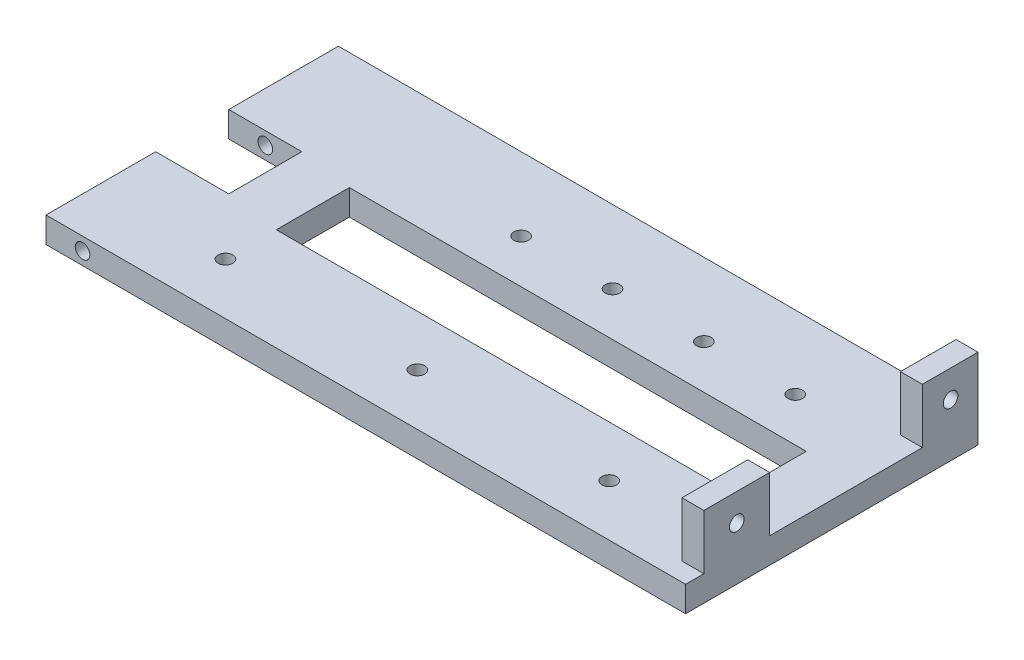
SolidWorks part; units mm, degrees
ref_plane "Front Plane" through (0, 0, 0) normal (0, 0, 1) x (1, 0, 0)
ref_plane "Top Plane" through (0, 0, 0) normal (0, 1, 0) x (1, 0, 0)
ref_plane "Right Plane" through (0, 0, 0) normal (1, 0, 0) x (0, 0, -1)
sketch "Sketch1" plane through (0, 0, 0) normal (0, 1, 0) x (1, 0, 0)
  line L1 (-89.8834, 33.007) -> (85.1166, 33.007)
  line L2 (-89.8834, 33.007) -> (-89.8834, -46.993)
  line L3 (-89.8834, -46.993) -> (85.1166, -46.993)
  line L4 (85.1166, 33.007) -> (85.1166, -46.993)
  dimension "D1" = 80
  dimension "D2" = 175
extrude "Boss-Extrude1" add sketch "Sketch1" along normal blind 7
sketch "Sketch2" plane through (0, 7, 0) normal (0, 1, 0) x (1, 0, 0)
  line L0 (-89.8834, -46.993) -> (85.1166, -46.993) construction
  line L1 (-89.8834, 33.007) -> (-89.8834, -46.993) construction
  line L2 (85.1166, -46.993) -> (85.1166, 33.007) construction
  circle A0 centre (-54.8834, -32.893) radius 2
  circle A1 centre (-2.3834, -32.893) radius 2
  circle A2 centre (50.1166, -32.893) radius 2
  dimension "D1" = 14.1
  dimension "D2" = 14.1
  dimension "D3" = 14.1
  dimension "D4" = 35
  dimension "D5" = 52.5
  dimension "D6" = 52.5
  dimension "D7" = 35
extrude "Cut-Extrude1" cut sketch "Sketch2" against normal blind 10
sketch "Sketch3" plane through (0, 7, 0) normal (0, 1, 0) x (1, 0, 0)
  line L1 (50.1166, -18.993) -> (-74.8834, -18.993)
  line L2 (50.1166, -18.993) -> (50.1166, 1.007)
  line L3 (50.1166, 1.007) -> (-74.8834, 1.007)
  line L4 (-74.8834, -18.993) -> (-74.8834, 1.007)
  line L6 (-89.8834, -46.993) -> (85.1166, -46.993) construction
  line L7 (-89.8834, 33.007) -> (-89.8834, -46.993) construction
  dimension "D1" = 125
  dimension "D2" = 28
  dimension "D3" = 15
  dimension "D4" = 20
extrude "Cut-Extrude2" cut sketch "Sketch3" against normal blind 1
sketch "Sketch7" plane through (0, 7, 0) normal (0, 1, 0) x (1, 0, 0)
  line L0 (-89.8834, 33.007) -> (-89.8834, -46.993) construction
  line L1 (-89.8834, 33.007) -> (-83.8834, 33.007)
  line L2 (-89.8834, 33.007) -> (-89.8834, 17.7803)
  line L3 (-89.8834, 17.7803) -> (-83.8834, 17.7803)
  line L4 (-83.8834, 33.007) -> (-83.8834, 17.7803)
  line L5 (-89.8834, -41.993) -> (-83.8834, -41.993)
  line L6 (-89.8834, -41.993) -> (-89.8834, -23.993)
  line L7 (-89.8834, -23.993) -> (-83.8834, -23.993)
  line L8 (-83.8834, -41.993) -> (-83.8834, -23.993)
  line L9 (-89.8834, -46.993) -> (85.1166, -46.993) construction
  dimension "D1" = 6
  dimension "D2" = 15.2267
  dimension "D3" = 5
  dimension "D4" = 18
  dimension "D5" = 6
extrude "Boss-Extrude3" add sketch "Sketch7" along normal blind 15
sketch "Sketch8" plane through (-83.8834, 0, 0) normal (1, 0, 0) x (0, 0, -1)
  line L0 (33.007, 22) -> (33.007, 7) construction
  line L1 (17.7803, 22) -> (33.007, 22) construction
  line L2 (-23.993, 22) -> (-23.993, 7) construction
  circle A0 centre (25.507, 14.5) radius 2
  circle A1 centre (-32.993, 14.5) radius 2
  dimension "D1" = 7.5
  dimension "D3" = 9
  dimension "D2" = 7.5
extrude "Cut-Extrude4" cut sketch "Sketch8" against normal blind 15
sketch "Sketch9" plane through (0, 0, 0) normal (0, -1, 0) x (1, 0, 0)
  line L0 (85.1166, 46.993) -> (85.1166, -33.007) construction
  line L1 (85.1166, 16.993) -> (65.1166, 16.993)
  line L2 (85.1166, 16.993) -> (85.1166, -3.007)
  line L3 (85.1166, -3.007) -> (65.1166, -3.007)
  line L4 (65.1166, 16.993) -> (65.1166, -3.007)
  line L5 (-89.8834, 46.993) -> (85.1166, 46.993) construction
  line L6 (85.1166, -33.007) -> (-89.8834, -33.007) construction
  dimension "D1" = 20
  dimension "D2" = 20
  dimension "D3" = 30
  dimension "D4" = 30
extrude "Cut-Extrude5" cut sketch "Sketch9" against normal blind 15
sketch "Sketch10" plane through (0, 0, -3.007) normal (0, 0, 1) x (1, 0, 0)
  line L0 (85.1166, 7) -> (85.1166, 0) construction
  line L1 (65.1166, 0) -> (85.1166, 0) construction
  circle A0 centre (75.1166, 3.5) radius 2
  dimension "D1" = 10
  dimension "D2" = 3.5
extrude "Cut-Extrude7" cut sketch "Sketch10" against normal through all both and the other way through all
extrude "Cut-Extrude8" cut sketch "Sketch3<3>" against normal blind 10
sketch "Sketch3<3>" plane through (0, 7, 0) normal (0, 1, 0) x (1, 0, 0) same geometry as "Sketch3"
sketch "Sketch11" plane through (0, 7, 0) normal (0, 1, 0) x (1, 0, 0)
  line L0 (50.1166, 1.007) -> (-74.8834, 1.007) construction
  line L1 (-74.8834, 1.007) -> (-74.8834, -18.993) construction
  circle A0 centre (-59.8834, 13.007) radius 2
  circle A1 centre (-34.8834, 13.007) radius 2
  circle A2 centre (-9.8834, 13.007) radius 2
  circle A3 centre (15.1166, 13.007) radius 2
  dimension "D1" = 12
  dimension "D2" = 12
  dimension "D3" = 12
  dimension "D4" = 12
  dimension "D5" = 15
  dimension "D6" = 25
  dimension "D7" = 25
  dimension "D8" = 25
extrude "Cut-Extrude9" cut sketch "Sketch11" against normal blind 10
mirror "Mirror2" about plane through (-89.8834, 7, -33.007) normal (1, 0, 0) of bodies 112
delete or keep bodies "Body-Delete/Keep 1" type delete bodies bodies 112
